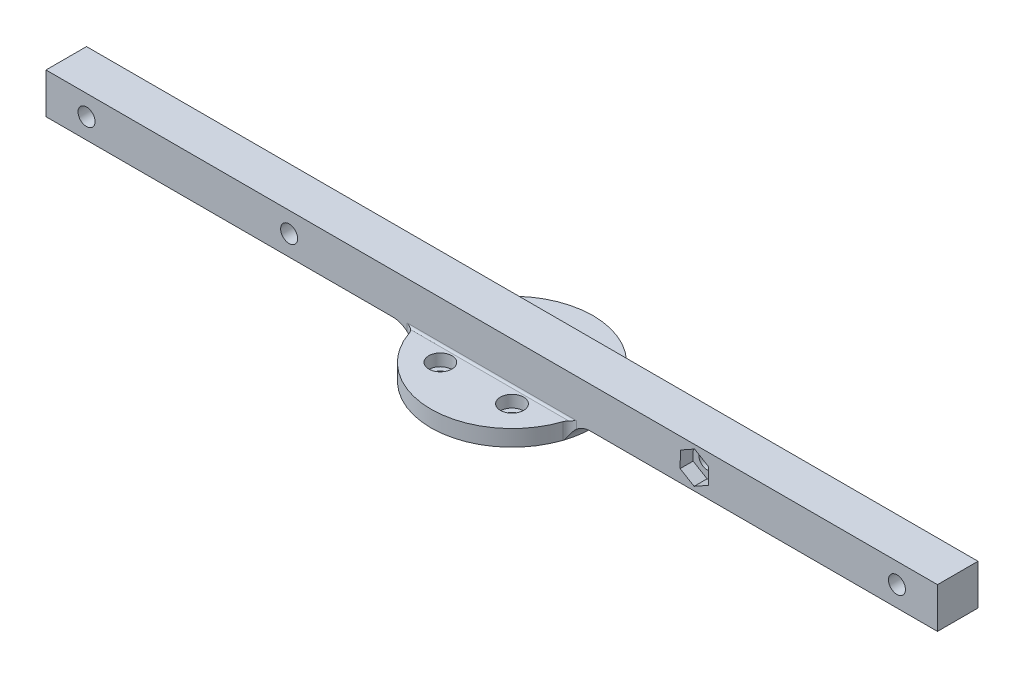
SolidWorks part; units mm, degrees
ref_plane "Front Plane" through (0, 0, 0) normal (0, 0, 1) x (1, 0, 0)
ref_plane "Top Plane" through (0, 0, 0) normal (0, 1, 0) x (1, 0, 0)
ref_plane "Right Plane" through (0, 0, 0) normal (1, 0, 0) x (0, 0, -1)
sketch "Sketch2" plane through (0, 0, 0) normal (0, 1, 0) x (1, 0, 0)
  line L0 (-79.7466, 0) -> (74.5182, 0) construction
  line L1 (-74.6554, -5) -> (-74.6554, 5)
  line L2 (-74.6554, 5) -> (145.3446, 5)
  line L3 (145.3446, 5) -> (145.3446, -5)
  line L4 (145.3446, 0) -> (-74.6554, 0)
  line L5 (-74.6554, -5) -> (145.3446, -5)
  dimension "D1" = 10
  dimension "D2" = 220
extrude "Boss-Extrude1" add sketch "Sketch2" along normal blind 10 contours L4 L3 L2 L1 | L1 L5 L3 L4 region at (35.3446, 0, 2.5) region at (35.3446, 0, -2.5)
sketch "Sketch3" plane through (0, 0, 0) normal (0, 1, 0) x (1, 0, 0)
  line L0 (-74.6554, -5) -> (-74.6554, 5) construction
  line L1 (-74.6554, -5) -> (145.3446, -5) construction
  circle A0 centre (35.3446, 0) radius 20
  dimension "D2" = 5
  dimension "D1" = 110
extrude "Boss-Extrude2" add sketch "Sketch3" against normal blind 4
fillet "Fillet1" radius 5 1 edges at (55.3446, 0, 0)
fillet "Fillet2" radius 5 1 edges at (15.3446, 0, 0)
fillet "Fillet3" radius 0.5 1 edges at (35.3446, 0, -5)
fillet "Fillet4" radius 0.5 1 edges at (35.3446, 0, 5)
fillet "Fillet7" radius 2 4 edges at (54.7096, -1.75, 5) (54.7096, -1.75, -5) (15.9797, -1.75, -5) (15.9797, -1.75, 5)
sketch "Sketch9" plane through (0, 25, -5) normal (0, 0, -1) x (1, 0, 0)
  line L0 (-74.6554, 15) -> (145.3446, 15) construction
  line B0 (-61.211, 17.9415) -> (-61.1505, 21.9536)
  line B1 (-61.1505, 21.9536) -> (-64.5948, 24.0121)
  line B2 (-64.5948, 24.0121) -> (-68.0997, 22.0585)
  line B3 (-68.0997, 22.0585) -> (-68.1602, 18.0464)
  line B4 (-68.1602, 18.0464) -> (-64.7159, 15.9879)
  line B5 (-64.7159, 15.9879) -> (-61.211, 17.9415)
  circle B6 centre (-64.6554, 20) radius 3.475 construction
  dimension "D1" = 5
sketch_block_instance "Block-Orthogonal mount (BB) lower jaw-1"
sketch_block "Block-Orthogonal mount (BB) lower jaw" parameters "D1"=6.95
sketch "Sketch11" plane through (0, 25, -5) normal (0, 0, -1) x (1, 0, 0)
  line L0 (-74.6554, 15) -> (145.3446, 15) construction
  line B0 (138.789, 17.9415) -> (138.8495, 21.9536)
  line B1 (138.8495, 21.9536) -> (135.4052, 24.0121)
  line B2 (135.4052, 24.0121) -> (131.9003, 22.0585)
  line B3 (131.9003, 22.0585) -> (131.8398, 18.0464)
  line B4 (131.8398, 18.0464) -> (135.2841, 15.9879)
  line B5 (135.2841, 15.9879) -> (138.789, 17.9415)
  circle B6 centre (135.3446, 20) radius 3.475 construction
  dimension "D1" = 5
sketch_block_instance "Block-Orthogonal mount (BB) lower jaw-4"
sketch "Sketch17" plane through (0, -4, 0) normal (0, -1, 0) x (-1, 0, 0)
  circle A0 centre (-44.1835, -8.8388) radius 1.6
  dimension "D1" = 3.2
  dimension "D2" = 12.5
extrude "Cut-Extrude14" cut sketch "Sketch17" against normal through all
pattern_circular "CirPattern1" count 4 over 360 about axis through (35.3446, -4, 0) along (0, 1, 0) of "Cut-Extrude14"
sketch "Sketch18" plane through (0, 0, 0) normal (0, 1, 0) x (1, 0, 0)
  circle A0 centre (26.5058, -8.8388) radius 2.86
extrude "Cut-Extrude15" cut sketch "Sketch18" against normal blind 2.95
pattern_circular "CirPattern2" count 4 over 360 about axis through (35.3446, 0, 0) along (0, 1, 0) of "Cut-Extrude15"
sketch "Sketch19" plane through (0, 0, 5) normal (0, 0, 1) x (1, 0, 0)
  line L0 (-74.6554, 10) -> (145.3446, 10) construction
  line L1 (145.3446, 10) -> (145.3446, 0) construction
  line B0 (88.789, 2.9415) -> (88.8495, 6.9536)
  line B1 (88.8495, 6.9536) -> (85.4052, 9.0121)
  line B2 (85.4052, 9.0121) -> (81.9003, 7.0585)
  line B3 (81.9003, 7.0585) -> (81.8398, 3.0464)
  line B4 (81.8398, 3.0464) -> (85.2841, 0.9879)
  line B5 (85.2841, 0.9879) -> (88.789, 2.9415)
  circle B6 centre (85.3446, 5) radius 3.475 construction
  dimension "D1" = 5
  dimension "D2" = 60
sketch_block_instance "M4 nut insert-1"
sketch "Sketch22" plane through (0, 0, 5) normal (0, 0, 1) x (1, 0, 0)
  circle A0 centre (85.3446, 5) radius 2.1
extrude "Cut-Extrude17" cut sketch "Sketch22" against normal through all
extrude "Cut-Extrude18" cut sketch "Sketch19" against normal blind 3.2
sketch "Sketch23" plane through (0, 0, -5) normal (0, 0, 1) x (1, 0, 0)
  line L0 (-74.6554, 10) -> (145.3446, 10) construction
  line L1 (-74.6554, 10) -> (-74.6554, 0) construction
  point P0 (-47.4293, 4.1471)
  line B0 (-11.211, 2.9415) -> (-11.1505, 6.9536)
  line B1 (-11.1505, 6.9536) -> (-14.5948, 9.0121)
  line B2 (-14.5948, 9.0121) -> (-18.0997, 7.0585)
  line B3 (-18.0997, 7.0585) -> (-18.1602, 3.0464)
  line B4 (-18.1602, 3.0464) -> (-14.7159, 0.9879)
  line B5 (-14.7159, 0.9879) -> (-11.211, 2.9415)
  circle B6 centre (-14.6554, 5) radius 3.475 construction
  dimension "D1" = 5
  dimension "D2" = 60
sketch_block_instance "Block-Orthogonal mount (BB) lower jaw-9"
sketch "Sketch24" plane through (0, 0, -5) normal (0, 0, -1) x (-1, 0, 0)
  circle A0 centre (-135.3446, 5) radius 2.1
  circle A1 centre (14.6554, 5) radius 2.1
  circle A2 centre (64.6554, 5) radius 2.1
extrude "Cut-Extrude20" cut sketch "Sketch24" against normal through all
extrude "Cut-Extrude22" cut sketch "Sketch23" along normal blind 3.2
extrude "Cut-Extrude23" cut sketch "Sketch9" against normal blind 3.2
extrude "Cut-Extrude24" cut sketch "Sketch11" against normal blind 3.2
